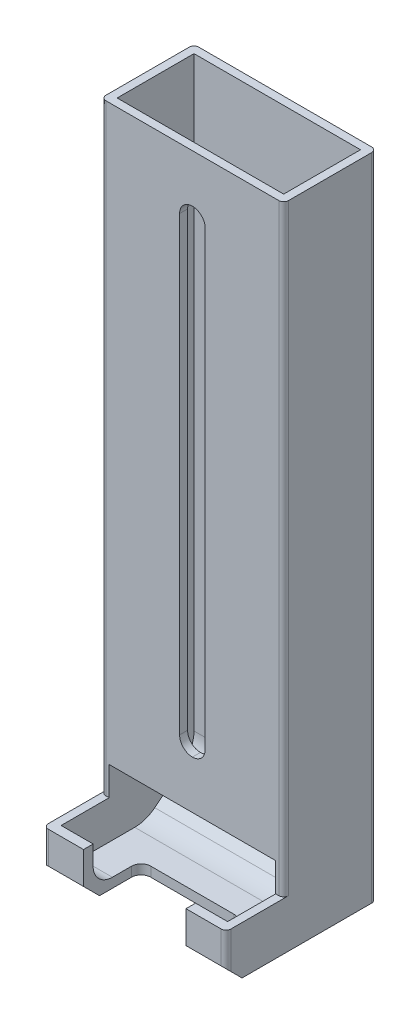
SolidWorks part; units mm, degrees
ref_plane "Front Plane" through (0, 0, 0) normal (0, 0, 1) x (1, 0, 0)
ref_plane "Top Plane" through (0, 0, 0) normal (0, 1, 0) x (1, 0, 0)
ref_plane "Right Plane" through (0, 0, 0) normal (1, 0, 0) x (0, 0, -1)
sketch "Sketch1" plane through (0, 0, 0) normal (0, 1, 0) x (1, 0, 0)
  line L1 (26, -12) -> (-26, -12)
  line L2 (26, -12) -> (26, 12)
  line L3 (26, 12) -> (-26, 12)
  line L4 (-26, -12) -> (-26, 12)
  line L5 (26, -12) -> (-26, 12) construction
  line L6 (26, 12) -> (-26, -12) construction
  line L7 (28.5, -14.5) -> (-28.5, -14.5)
  line L8 (28.5, -14.5) -> (28.5, 14.5)
  line L9 (28.5, 14.5) -> (-28.5, 14.5)
  line L10 (-28.5, -14.5) -> (-28.5, 14.5)
  line L11 (28.5, -14.5) -> (-28.5, 14.5) construction
  line L12 (28.5, 14.5) -> (-28.5, -14.5) construction
  point P0 (0, 0)
  point P6 (0, 0)
  dimension "D1" = 24
  dimension "D2" = 52
  dimension "D3" = 2.5
  dimension "D4" = 2.5
extrude "Boss-Extrude1" add sketch "Sketch1" along normal blind 200
sketch "Sketch2" plane through (0, 0, 0) normal (0, -1, 0) x (1, 0, 0)
  line L1 (28.5, -14.5) -> (-28.5, -14.5)
  line L2 (28.5, -14.5) -> (28.5, 14.5)
  line L4 (-28.5, -14.5) -> (-28.5, 14.5)
  line L5 (28.5, -14.5) -> (-28.5, 14.5) construction
  line L6 (28.5, 14.5) -> (-28.5, -14.5) construction
  line L9 (28.5, 14.5) -> (-28.5, 14.5)
  point P0 (0, 0)
extrude "Boss-Extrude2" add sketch "Sketch2" along normal blind 3
sketch "Sketch5" plane through (28.5, 0, 0) normal (1, 0, 0) x (0, 0, -1)
  line L0 (14.5, 200) -> (14.5, -3) construction
  line L3 (24.45, 24.3602) -> (14.5, 29)
  line L13 (24.45, 17) -> (24.45, 24.3602)
  line L15 (14.75, 18.5) -> (14.75, 17)
  line L16 (14.75, 17) -> (14.5, 17)
  line L20 (20.45, 18.5) -> (20.45, 17)
  line L21 (20.45, 17) -> (24.45, 17)
  line L22 (14.5, 29) -> (14.5, 17)
  line L23 (14.5, -3) -> (-14.5, -3) construction
  arc A6 (20.45, 18.5) -> (14.75, 18.5) centre (17.6, 19.4367) ccw
  dimension "D1" = 3
  dimension "D6" = 3.1
  dimension "D2" = 0.25
  dimension "D3" = 12
  dimension "D4" = 1.5
  dimension "D5" = 65
  dimension "D7" = 20
  dimension "D8" = 4
extrude "Boss-Extrude3" add sketch "Sketch5" against normal blind 35 from offset 11 offset against normal yes
chamfer "Chamfer1" distance 0.25 angle 45 2 edges at (0, 17, -20.45) (0, 17, -14.75)
pattern_linear "LPattern1" count 2 spacing 58.25 along (0, 1, 0) of "Boss-Extrude3"
sketch "Sketch9" plane through (0, 0, 12) normal (0, 0, -1) x (-1, 0, 0)
  line L0 (26, 200) -> (26, 0) construction
  line L1 (-26, 0) -> (26, 0)
  line L2 (-26, 0) -> (-26, 21)
  line L3 (-26, 21) -> (26, 21)
  line L4 (26, 0) -> (26, 21)
  dimension "D1" = 21
extrude "Cut-Extrude1" cut sketch "Sketch9" against normal through all
chamfer "Chamfer2" distance 12 distance2 15 1 edges at (0, 0, -12) first distance on face at (0, 100, -12)
sketch "Sketch10" plane through (28.5, 0, 0) normal (1, 0, 0) x (0, 0, -1)
  line L0 (-14.5, -3) -> (-32.5, -3)
  line L1 (-32.5, -3) -> (-32.5, 12)
  line L2 (-32.5, 12) -> (-14.5, 12)
  line L3 (-14.5, 200) -> (-14.5, -3) construction
  line L4 (-14.5, 12) -> (-14.5, -3)
  dimension "D1" = 18
  dimension "D2" = 15
extrude "Boss-Extrude4" add sketch "Sketch10" against normal up to surface (2.5 mm away) up to face at (26, 64.8571, 4.5714)
sketch "Sketch11" plane through (26, 0, 0) normal (-1, 0, 0) x (0, 0, 1)
  line L0 (14.5, 0) -> (29.5, 0)
  line L1 (29.5, 0) -> (29.5, 12)
  line L2 (14.5, 12) -> (32.5, 12) construction
  line L3 (29.5, 12) -> (32.5, 12)
  line L4 (32.5, 12) -> (32.5, -3)
  line L5 (32.5, -3) -> (14.5, -3)
  line L6 (14.5, -3) -> (14.5, 0)
  dimension "D1" = 3
extrude "Boss-Extrude5" add sketch "Sketch11" along normal blind 10
ref_plane "Plane1" through (0, 0, 0) normal (1, 0, 0) x (0, 0, -1)
mirror "Mirror1" about plane through (0, 0, 0) normal (1, 0, 0) of "Boss-Extrude5"
sketch "Sketch12" plane through (-26, 0, 0) normal (-1, 0, 0) x (0, 0, 1)
  line L1 (14.5, -3) -> (32.5, -3)
  line L2 (14.5, -3) -> (14.5, 12)
  line L3 (14.5, 12) -> (32.5, 12)
  line L4 (32.5, -3) -> (32.5, 12)
extrude "Boss-Extrude6" add sketch "Sketch12" along normal up to surface (2.5 mm away) up to face at (-28.5, 98.5, 0)
sketch "Sketch13" plane through (0, 0, 14.5) normal (0, 0, 1) x (1, 0, 0)
  line L0 (-28.5, 200) -> (28.5, 200) construction
  line L1 (4, 36) -> (-4, 36)
  line L2 (4, 36) -> (4, 185)
  line L3 (4, 185) -> (-4, 185)
  line L4 (-4, 36) -> (-4, 185)
  line L5 (4, 36) -> (-4, 185) construction
  line L6 (4, 185) -> (-4, 36) construction
  line L7 (-26, 21) -> (26, 21) construction
  point P0 (0, 110.5)
  point P9 (4.9627, 36)
  point P10 (0, 0)
  dimension "D1" = 15
  dimension "D2" = 15
  dimension "D3" = 8
extrude "Cut-Extrude2" cut sketch "Sketch13" against normal up to surface (2.5 mm away) up to face at (0, 110.5, 12)
fillet "Fillet11" radius 4 4 edges at (-4, 185, 13.25) (4, 185, 13.25) (-4, 36, 13.25) (4, 36, 13.25)
fillet "Fillet7" radius 6 2 edges at (21, 0, 29.5) (-21, 0, 29.5)
chamfer "Chamfer3" distance 5 angle 45 2 edges at (22.25, -3, 32.5) (-22.25, -3, 32.5)
fillet "Fillet8" radius 1.5 6 edges at (-28.5, 7, 32.5) (28.5, 7, 32.5) (28.5, 98.5, -14.5) (-28.5, 98.5, -14.5) (-28.5, 106, 14.5) (28.5, 106, 14.5)
fillet "Fillet9" radius 3 2 edges at (16, -1.5, 14.5) (-16, -1.5, 14.5)
fillet "Fillet10" radius 10 2 edges at (0, 0, 3) (0, 12, -12)
sketch "Sketch14" plane through (-26, 0, 0) normal (1, 0, 0) x (0, 0, -1)
  line L0 (-12, 21) -> (-8.5, 21)
  line L1 (-8.5, 21) -> (-12, 31)
  line L2 (-12, 200) -> (-12, 21) construction
  line L3 (-12, 31) -> (-12, 21)
  dimension "D1" = 3.5
  dimension "D2" = 10
extrude "Boss-Extrude7" add sketch "Sketch14" along normal up to surface (52 mm away) up to face at (26, 41.4827, 9.1824)
fillet "Fillet12" radius 2 4 edges at (17.5, 23, -14.5) (17.5, 81.25, -14.5) (-17.5, 23, -14.5) (-17.5, 81.25, -14.5)
